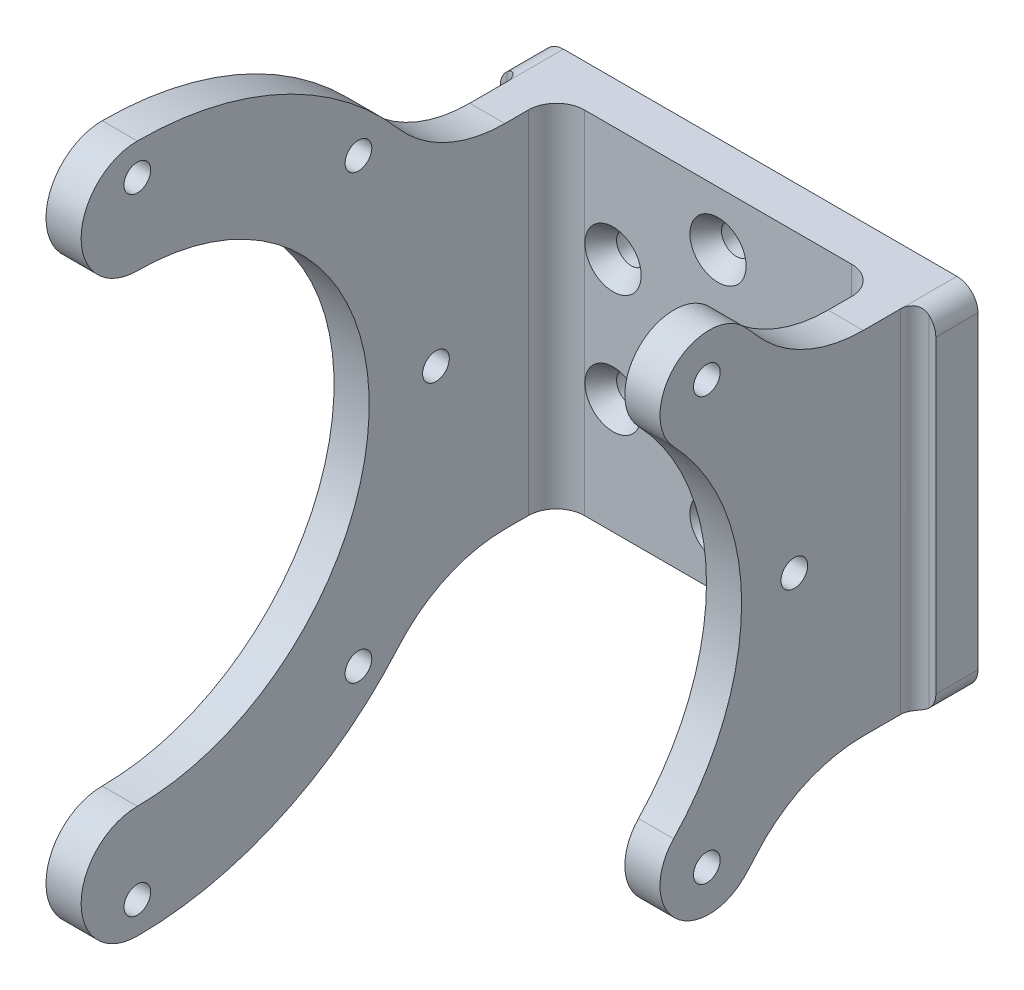
SolidWorks part; units mm, degrees
note: '?' marks a value the reader was unsure of.
ref_plane "前视基准面" through (0, 0, 0) normal (0, 0, 1) x (1, 0, 0)
ref_plane "上视基准面" through (0, 0, 0) normal (0, 1, 0) x (1, 0, 0)
ref_plane "右视基准面" through (0, 0, 0) normal (1, 0, 0) x (0, 0, -1)
other "Configuration Table"
sketch "草图1" plane through (0, 0, 0) normal (0, 0, 1) x (1, 0, 0)
  line L0 (0, 30) -> (0, -30) construction
  circle A0 centre (0, 0) radius 30
  circle A1 centre (0, 0) radius 17.25 construction
  circle A2 centre (0, 17.25) radius 2.1
  circle A3 centre (14.9389, 8.625) radius 2.1
  circle A4 centre (14.9389, -8.625) radius 2.1
  circle A5 centre (0, -17.25) radius 2.1
  circle A6 centre (-14.9389, -8.625) radius 2.1
  circle A7 centre (-14.9389, 8.625) radius 2.1
  point P20 (0, 0)
  dimension "D1" = 60
  dimension "D2" = 34.5
  dimension "D3" = 4.2
  dimension "D6" = 17.25
  dimension "D4" = 6
extrude "凸台-拉伸1" add sketch "草图1" along normal blind 6
sketch "草图2" plane through (0, 0, 6) normal (0, 0, 1) x (1, 0, 0)
  line L1 (-34, 34) -> (34, 34)
  line L2 (-34, 34) -> (-34, -34)
  line L3 (-34, -34) -> (34, -34)
  line L4 (34, 34) -> (34, -34)
  line L5 (-34, 34) -> (34, -34) construction
  line L6 (-34, -34) -> (34, 34) construction
  circle A0 centre (0, 0) radius 30 construction
  circle A1 centre (0, 0) radius 30
  point P0 (0, 0)
  dimension "D1" = 68
  dimension "D2" = 68
extrude "凸台-拉伸2" add sketch "草图2" against normal blind 6
fillet "圆角1" radius 12 4 edges at (34, -34, 3) (-34, -34, 3) (-34, 34, 3) (34, 34, 3)
ref_axis "基准轴1" through (-14.9389, 8.625, 6) along (0, 0, -1)?
ref_plane "基准面1" through (-14.9389, 0, 0) normal (-1, 0, 0) x (0, 0, -1)
sketch "草图4" plane through (-14.9389, 0, 0) normal (-1, 0, 0) x (0, 0, -1)
  line L0 (-6, -6.525) -> (-6, -10.725) construction
  line L1 (-6, -6.525) -> (-6, -10.725)
  line L2 (-6, -8.625) -> (0, -8.625) construction
  line L3 (0, -22) -> (0, 22) construction
  line L4 (-6, -8.625) -> (0, -8.625) construction
  line L5 (-6, -8.625) -> (-6, -12.625)
  line L6 (-6, -22) -> (-6, 22) construction
  line L7 (-6, -12.625) -> (-3.4, -10.725)
  line L8 (-3.4, -10.725) -> (-3.4, -8.625)
  line L9 (-3.4, -8.625) -> (-6, -8.625)
  dimension "D1" = 4
  dimension "D2" = 2.1
  dimension "D3" = 2.6
revolve "切除-旋转1" cut sketch "草图4" angle 360 about L2
sketch "草图5" plane through (0, 0, 0) normal (0, 1, 0) x (1, 0, 0)
  line L0 (0, 0) -> (0, 13.7569) construction
  line L1 (22, 0) -> (-22, 0) construction
pattern_circular "阵列(圆周)1" count 6 every 60 about axis through (0, 0, 0) along (0, 0, 1) of "切除-旋转1"
ref_plane "基准面2" through (28, 0, 0) normal (1, 0, 0) x (0, 0, -1)
sketch "草图6" plane through (28, 0, 0) normal (1, 0, 0) x (0, 0, -1)
  line L0 (0, 0) -> (-6, 0) construction
  line L1 (-6, 25) -> (-6, -25)
  line L2 (-6, 0) -> (-65.6426, 0) construction
  line L3 (-6, 25) -> (-23.5, 25)
  line L4 (-6, 22) -> (-6, -22)
  line L5 (-6, -22) -> (0, -22)
  line L6 (0, -22) -> (0, 22)
  line L7 (0, 22) -> (-6, 22)
  line L8 (-6, 22) -> (-6, -22)
  line L9 (-6, -22) -> (0, -22)
  line L10 (0, -22) -> (0, 22)
  line L11 (0, 22) -> (-6, 22)
  line L12 (-6, -25) -> (-23.5, -25)
  circle A0 centre (-65.6426, 0) radius 42.5 construction
  circle A1 centre (-65.6426, 0) radius 49
  circle A2 centre (-65.6426, 0) radius 35
  circle A3 centre (-23.1426, 0) radius 1.9
  circle A4 centre (-35.5906, -30.052) radius 1.9
  circle A5 centre (-65.6426, -42.5) radius 1.9
  circle A6 centre (-95.6947, -30.052) radius 1.9
  circle A7 centre (-108.1426, 0) radius 1.9
  circle A8 centre (-95.6947, 30.052) radius 1.9
  circle A9 centre (-65.6426, 42.5) radius 1.9
  circle A10 centre (-35.5906, 30.052) radius 1.9
  circle A11 centre (-35.2617, 29) radius 7
  circle A12 centre (-35.2617, -29) radius 7
  point P32 (-65.6426, 0)
  dimension "D3" = 85
  dimension "D4" = 98
  dimension "D5" = 70
  dimension "D6" = 3.8
  dimension "D10" = 58
  dimension "D2" = 50
  dimension "D8" = 45
  dimension "D9" = 17.5
  dimension "D1" = 0
  dimension "D7" = 8
extrude "凸台-拉伸3" add sketch "草图6" against normal blind 5 contours A1 L12 L1 L3 | A12 A1 A11 A2 A3 | A11 A10 | A12 A4
fillet "圆角2" radius 20 2 edges at (25.5, 25, 23.5) (25.5, -25, 23.5)
sketch "草图7" plane through (0, 0, 6) normal (0, 0, 1) x (1, 0, 0)
  line L1 (-34, 0) -> (34, 0) construction
  line L2 (-31, 25) -> (31, 25)
  line L3 (-31, 25) -> (-31, -25)
  line L4 (34, 34) -> (-34, 34)
  line L5 (34, -34) -> (34, 34)
  line L6 (-34, -34) -> (34, -34)
  line L7 (-34, 34) -> (-34, -34)
  line L8 (34, 34) -> (-34, 34)
  line L9 (34, -34) -> (34, 34)
  line L10 (-34, -34) -> (34, -34)
  line L11 (-34, 34) -> (-34, -34)
  line L12 (-31, -25) -> (31, -25)
  line L13 (31, 25) -> (31, -25)
  line L14 (-31, 25) -> (31, -25) construction
  line L15 (-31, -25) -> (31, 25) construction
  circle A1 centre (0, 0) radius 30
  circle A2 centre (0, 0) radius 30
  line M15 (-22, -34) -> (22, -34)
  arc M16 (22, -34) -> (34, -22) centre (22, -22) ccw
  line M17 (34, -22) -> (34, 22)
  arc M18 (34, 22) -> (22, 34) centre (22, 22) ccw
  line M19 (22, 34) -> (-22, 34)
  arc M20 (-22, 34) -> (-34, 22) centre (-22, 22) ccw
  line M21 (-34, 22) -> (-34, -22)
  arc M22 (-34, -22) -> (-22, -34) centre (-22, -22) ccw
  dimension "D3" = 50
  dimension "D4" = 62
  dimension "D1" = 0
  dimension "D2" = 0
extrude "切除-拉伸2" cut sketch "草图7" against normal blind 64 contours A2 L2 L13 L12 L3 M22 M15 M16 M17 M18 M19 M20 M21 | L12 A2 | L2 A2
ref_plane "基准面3" through (-28, 0, 0) normal (-1, 0, 0) x (0, 0, 1)
sketch "草图9" plane through (-28, 0, 0) normal (-1, 0, 0) x (0, 0, 1)
  line L0 (0, 0) -> (65.6426, 0) construction
  line L1 (23.5, -25) -> (0, -25)
  line L4 (0, 25) -> (0, -25)
  line L5 (0, -25) -> (6, -25)
  line L6 (6, -25) -> (6, 25)
  line L7 (6, 25) -> (0, 25)
  line L8 (0, 25) -> (0, -25)
  line L9 (0, -25) -> (6, -25)
  line L10 (6, -25) -> (6, 25)
  line L11 (23.5, 25) -> (0, 25)
  circle A0 centre (65.6426, 0) radius 49
  circle A1 centre (65.6426, 0) radius 44.5 construction
  circle A2 centre (65.6426, 0) radius 42.5 construction
  circle A3 centre (65.6426, 0) radius 33
  circle A4 centre (23.1426, 0) radius 1.9
  circle A5 centre (21.1426, 0) radius 1.9
  circle A6 centre (34.1764, 31.4663) radius 1.9
  circle A7 centre (35.5906, 30.052) radius 1.9
  circle A8 centre (65.6426, 44.5) radius 1.9
  circle A9 centre (65.6426, 42.5) radius 1.9
  circle A10 centre (97.1089, 31.4663) radius 1.9
  circle A11 centre (95.6947, 30.052) radius 1.9
  circle A12 centre (110.1426, 0) radius 1.9
  circle A13 centre (108.1426, 0) radius 1.9
  circle A14 centre (97.1089, -31.4663) radius 1.9
  circle A15 centre (95.6947, -30.052) radius 1.9
  circle A16 centre (65.6426, -44.5) radius 1.9
  circle A17 centre (65.6426, -42.5) radius 1.9
  circle A18 centre (34.1764, -31.4663) radius 1.9
  circle A19 centre (35.5906, -30.052) radius 1.9
  circle A20 centre (102.9521, 17) radius 8
  circle A21 centre (102.9521, -17) radius 8
  point P48 (65.6426, 0)
  dimension "D2" = 98
  dimension "D3" = 66
  dimension "D4" = 89
  dimension "D5" = 85
  dimension "D6" = 3.8
  dimension "D7" = 3.8
  dimension "D8" = 8
  dimension "D10" = 34
  dimension "D9" = 17.5
  dimension "D1" = 0
extrude "凸台-拉伸4" add sketch "草图9" against normal blind 5 contours A0 L11 L10 L1 | A21 A3 A20 A0 A5 A4 A7 A6 A9 A8 A11 A10 A15 A14 A17 A16 A19 A18 | A20 | A21 | A4 A5 | A18 A19 | A16 A17 | A14 A15 | A6 A7 | A8 A9 | A10 A11
fillet "圆角6" radius 20 2 edges at (-25.5, 25, 23.5) (-25.5, -25, 23.5)
fillet "圆角8" radius 3 8 edges at (-31, 25, 3) (-31, -25, 3) (-29.5, -25, 6) (29.5, -25, 6) (31, -25, 3) (31, 25, 3) (-29.5, 25, 6) (29.5, 25, 6)
sketch "草图11" plane through (0, 0, 6) normal (0, 0, 1) x (1, 0, 0)
  circle A0 centre (0, 0) radius 7
  dimension "D1" = 14
extrude "切除-拉伸3" cut sketch "草图11" against normal blind 13
fillet "圆角9" radius 4 2 edges at (-23, 0, 6) (23, 0, 6)
fillet "圆角10" radius 2 2 edges at (28, 0, 6) (-28, 0, 6)
sketch "草图12" plane through (-28, 0, 0) normal (-1, 0, 0) x (0, 0, 1)
  line L0 (0, 0) -> (32.6426, 0) construction
  line L3 (13.3358, 25) -> (8, 25)
  line L4 (8, 25) -> (8, -25)
  line L5 (8, -25) -> (13.3358, -25)
  line L6 (13.3358, 25) -> (8, 25)
  line L7 (8, 25) -> (8, -25)
  line L8 (8, -25) -> (13.3358, -25)
  circle A0 centre (65.6426, 41) radius 8
  circle A1 centre (65.6426, -41) radius 8
  arc A7 (28.4972, -31.9565) -> (13.3358, -25) centre (13.3358, -45) ccw
  arc A8 (28.4972, -31.9565) -> (110.232, -20.3171) centre (65.6426, 0) ccw
  arc A9 (110.232, -20.3171) -> (95.6722, -13.6829) centre (102.9521, -17) ccw
  arc A10 (95.6722, 13.6829) -> (95.6722, -13.6829) centre (65.6426, 0) ccw
  arc A11 (95.6722, 13.6829) -> (110.232, 20.3171) centre (102.9521, 17) ccw
  arc A12 (110.232, 20.3171) -> (28.4972, 31.9565) centre (65.6426, 0) ccw
  arc A13 (13.3358, 25) -> (28.4972, 31.9565) centre (13.3358, 45) ccw
  arc A14 (28.4972, -31.9565) -> (13.3358, -25) centre (13.3358, -45) ccw
  arc A15 (28.4972, -31.9565) -> (110.232, -20.3171) centre (65.6426, 0) ccw
  arc A16 (110.232, -20.3171) -> (95.6722, -13.6829) centre (102.9521, -17) ccw
  arc A17 (95.6722, 13.6829) -> (95.6722, -13.6829) centre (65.6426, 0) ccw
  arc A18 (95.6722, 13.6829) -> (110.232, 20.3171) centre (102.9521, 17) ccw
  arc A19 (110.232, 20.3171) -> (28.4972, 31.9565) centre (65.6426, 0) ccw
  arc A20 (13.3358, 25) -> (28.4972, 31.9565) centre (13.3358, 45) ccw
  arc M18 (28.4972, -31.9565) -> (110.232, -20.3171) centre (65.6426, 0) ccw
  arc M19 (110.232, -20.3171) -> (95.6722, -13.6829) centre (102.9521, -17) ccw
  arc M20 (95.6722, -13.6829) -> (95.6722, 13.6829) centre (65.6426, 0) cw
  arc M21 (95.6722, 13.6829) -> (110.232, 20.3171) centre (102.9521, 17) ccw
  arc M22 (110.232, 20.3171) -> (28.4972, 31.9565) centre (65.6426, 0) ccw
  circle M27 centre (97.1089, 31.4663) radius 1.9
  circle M28 centre (97.1089, -31.4663) radius 1.9
  dimension "D2" = 82
  dimension "D1" = 0
extrude "切除-拉伸4" cut sketch "草图12" against normal blind 10 contours A0 M20 M21 M22 M27 | A1 M18 M19 M20 M28
